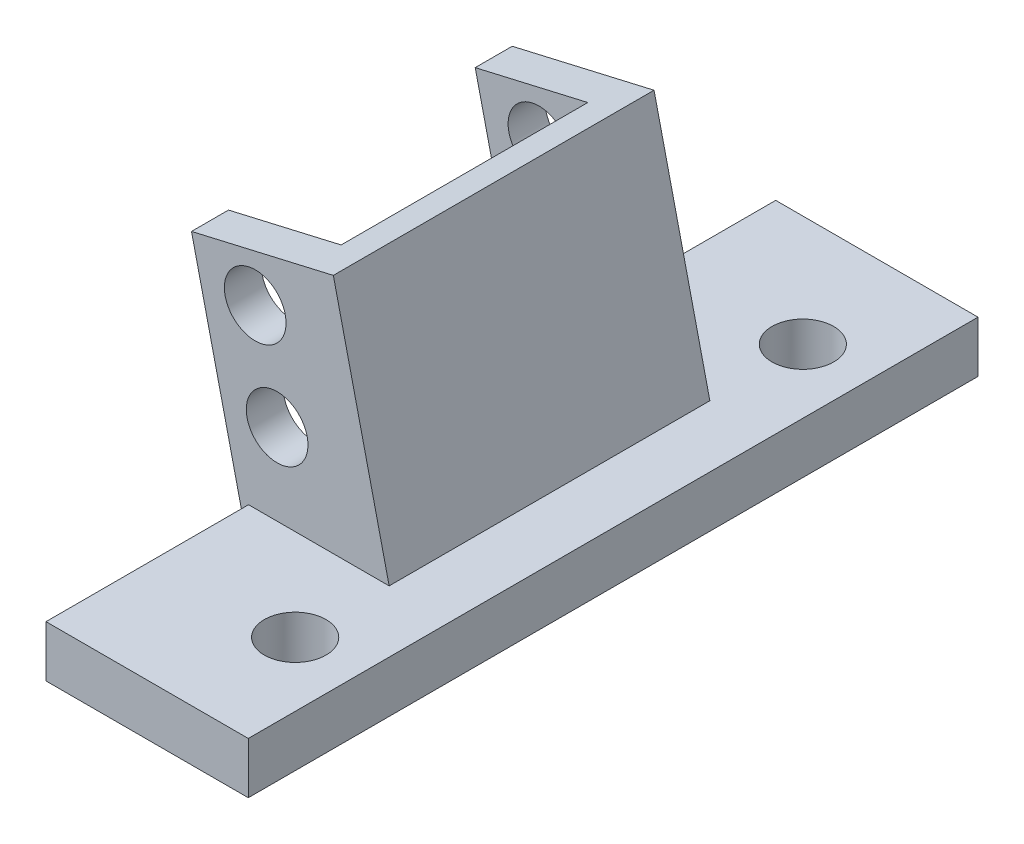
SolidWorks part; units mm, degrees
ref_plane "Front Plane" through (0, 0, 0) normal (0, 0, 1) x (1, 0, 0)
ref_plane "Top Plane" through (0, 0, 0) normal (0, 1, 0) x (1, 0, 0)
ref_plane "Right Plane" through (0, 0, 0) normal (1, 0, 0) x (0, 0, -1)
sketch "Sketch1" plane through (0, 0, 0) normal (0, 0, 1) x (1, 0, 0)
  line L0 (347.1928, 233.3099) -> (352.9388, 208.4948)
  line L1 (338.8256, 231.3724) -> (358.7891, 235.995) construction
  line L2 (352.9388, 208.4948) -> (367.5429, 211.8764)
  line L3 (367.5429, 211.8764) -> (361.7969, 236.6915)
  line L4 (361.7969, 236.6915) -> (347.1928, 233.3099)
  line L5 (338.6024, 208.4556) -> (357.7178, 212.8818) construction
  line L6 (338.6024, 208.4556) -> (357.7178, 212.8818)
  line L7 (352.2179, 211.6083) -> (357.7178, 212.8818)
  arc A0 (361.4826, 228.7505) -> (358.7891, 235.995) centre (353.7541, 230) ccw construction
  arc A1 (361.4826, 228.7505) -> (362.3955, 224.3254) centre (367.7512, 227.737) ccw construction
  arc A2 (362.9827, 217.3077) -> (362.3955, 224.3254) centre (356.0099, 220.2578) ccw construction
  arc A3 (357.7178, 212.8818) -> (362.9827, 217.3077) centre (356.0099, 220.2578) ccw construction
  arc A4 (361.4826, 228.7505) -> (358.7891, 235.995) centre (353.7541, 230) ccw
  arc A5 (361.4826, 228.7505) -> (362.3955, 224.3254) centre (367.7512, 227.737) ccw
  arc A6 (362.9827, 217.3077) -> (362.3955, 224.3254) centre (356.0099, 220.2578) ccw
  arc A7 (357.7178, 212.8818) -> (362.9827, 217.3077) centre (356.0099, 220.2578) ccw
  arc A8 (357.7178, 212.8818) -> (362.9827, 217.3077) centre (356.0099, 220.2578) ccw
  arc A9 (362.9827, 217.3077) -> (362.3955, 224.3254) centre (356.0099, 220.2578) ccw
  arc A10 (362.3955, 224.3254) -> (361.4826, 228.7505) centre (367.7512, 227.737) cw
  arc A11 (361.4826, 228.7505) -> (358.7891, 235.995) centre (353.7541, 230) ccw
extrude "Boss-Extrude1" add sketch "Sketch1" against normal blind 29.21 contours A7 L6 L0 L2 L3 L4 A4 A5 A6 region at (355.0403, 211.9324, 0)
sketch "Sketch2" plane through (0, 0, -29.21) normal (0, 0, -1) x (-1, 0, 0)
  line L0 (-358.7891, 235.995) -> (-347.1928, 233.3099)
  line L1 (-347.1928, 233.3099) -> (-352.2179, 211.6083)
  line L2 (-352.2179, 211.6083) -> (-357.7178, 212.8818)
  arc A0 (-357.7178, 212.8818) -> (-362.3955, 224.3254) centre (-356.0099, 220.2578) cw
  arc A1 (-362.3955, 224.3254) -> (-361.4826, 228.7505) centre (-367.7512, 227.737) ccw
  arc A2 (-361.4826, 228.7505) -> (-358.7891, 235.995) centre (-353.7541, 230) cw
  circle A3 centre (-353.7541, 230) radius 3.175 construction
  circle A4 centre (-356.0099, 220.2578) radius 3.175 construction
  circle A5 centre (-353.7541, 230) radius 3.175
  circle A6 centre (-356.0099, 220.2578) radius 3.175
  circle A7 centre (-356.0099, 220.2578) radius 3.175
  circle A8 centre (-353.7541, 230) radius 3.175
  arc M8 (-357.7178, 212.8818) -> (-362.3955, 224.3254) centre (-356.0099, 220.2578) cw
  arc M9 (-362.3955, 224.3254) -> (-361.4826, 228.7505) centre (-367.7512, 227.737) ccw
  arc M10 (-361.4826, 228.7505) -> (-358.7891, 235.995) centre (-353.7541, 230) cw
  line M15 (-352.2179, 211.6083) -> (-357.7178, 212.8818)
extrude "Boss-Extrude2" add sketch "Sketch2" against normal up to surface (3.81 mm away) contours L1 L0 A6 A5 M10 M9 M8 M15 region at (356.0136, 223.9731, -29.21)
sketch "Sketch3" plane through (0, 0, 0) normal (0, 0, 1) x (1, 0, 0)
  line L0 (347.1928, 233.3099) -> (352.9388, 208.4948)
  line L1 (352.9388, 208.4948) -> (367.5429, 211.8764)
  line L2 (367.5429, 211.8764) -> (361.7969, 236.6915)
  line L3 (361.7969, 236.6915) -> (347.1928, 233.3099)
  circle A0 centre (356.0099, 220.2578) radius 3.175 construction
  circle A1 centre (353.7541, 230) radius 3.175 construction
  circle A2 centre (356.0099, 220.2578) radius 3.175
  circle A3 centre (353.7541, 230) radius 3.175
  circle A4 centre (353.7541, 230) radius 3.175
  circle A5 centre (356.0099, 220.2578) radius 3.175
  arc M6 (362.3955, 224.3254) -> (357.7178, 212.8818) centre (356.0099, 220.2578) cw
  line M7 (357.7178, 212.8818) -> (352.2179, 211.6083)
  line M8 (352.2179, 211.6083) -> (352.9388, 208.4948)
  line M9 (352.9388, 208.4948) -> (367.5429, 211.8764)
  line M10 (367.5429, 211.8764) -> (361.7969, 236.6915)
  line M11 (361.7969, 236.6915) -> (358.7891, 235.995)
  arc M12 (358.7891, 235.995) -> (361.4826, 228.7505) centre (353.7541, 230) cw
  arc M13 (361.4826, 228.7505) -> (362.3955, 224.3254) centre (367.7512, 227.737) ccw
extrude "Boss-Extrude3" add sketch "Sketch3" along normal blind 3.81 contours L3 L0 A3 A2 M12 M7 M6 M13 | M13 M6 M7 M8 M9 M10 M11 M12 region at (356.0136, 223.9731, 0) region at (355.0403, 211.9324, 0)
ref_plane "Plane1" through (0, 211.8764, 0) normal (0, 1, 0) x (1, 0, 0)
sketch "Sketch5" plane through (0, 211.8764, 0) normal (0, 1, 0) x (1, 0, 0)
  line L0 (367.5429, 29.21) -> (367.5429, -3.81) construction
  line L1 (353.0649, 50.4669) -> (373.8929, 50.4669)
  line L2 (353.0649, 50.4669) -> (353.0649, -24.6621)
  line L3 (353.0649, -24.6621) -> (373.8929, -24.6621)
  line L4 (373.8929, 50.4669) -> (373.8929, -24.6621)
  circle A0 centre (363.409, 39.0369) radius 3.175
  circle A1 centre (363.9438, -13.2321) radius 3.175
  dimension "D1" = 6.35
  dimension "D6" = 6.35
  dimension "D2" = 20.828
  dimension "D3" = 6.35
  dimension "D4" = 11.43
  dimension "D5" = 11.43
extrude "Boss-Extrude4" add sketch "Sketch5" against normal blind 5.2893 contours L2 L1 L4 L3
sketch "Sketch8" plane through (0, 211.8764, 0) normal (0, 1, 0) x (1, 0, 0)
  line L0 (353.0649, 50.4669) -> (373.8929, 50.4669) construction
  line L1 (373.8929, 50.4669) -> (373.8929, -24.6621) construction
  line L2 (353.0649, -24.6621) -> (373.8929, -24.6621) construction
  circle A0 centre (367.2889, 39.0369) radius 3.175
  circle A1 centre (367.2889, -13.2321) radius 3.175
  dimension "D1" = 11.43
  dimension "D3" = 6.604
  dimension "D2" = 6.604
  dimension "D4" = 11.43
extrude "Cut-Extrude1" cut sketch "Sketch8" against normal blind 6.35
